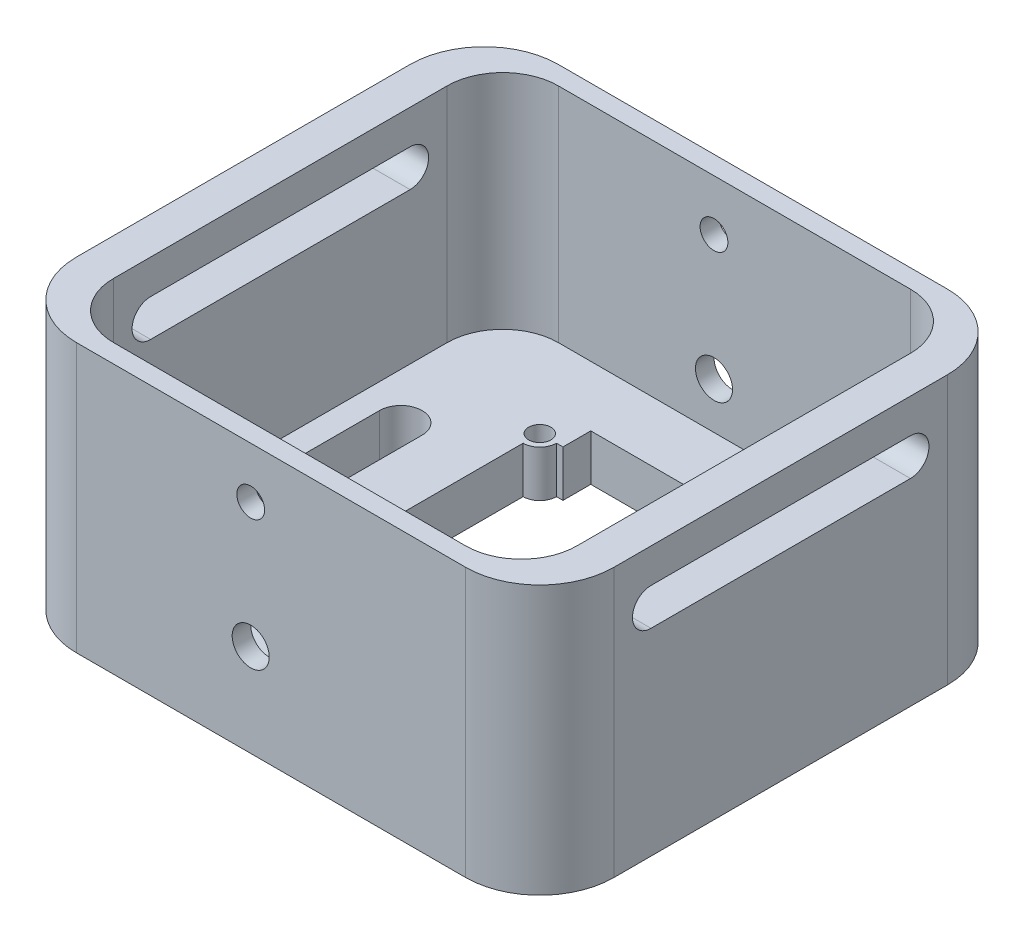
SolidWorks part; units mm, degrees
ref_plane "Front" through (0, 0, 0) normal (0, 0, 1) x (1, 0, 0)
ref_plane "Top" through (0, 0, 0) normal (0, 1, 0) x (1, 0, 0)
ref_plane "Right" through (0, 0, 0) normal (1, 0, 0) x (0, 0, -1)
sketch "Sketch1" plane through (0, 0, 0) normal (0, 1, 0) x (1, 0, 0)
  line L0 (1, 0) -> (12.5, 0) construction
  line L1 (-12.5, -12) -> (12.5, -12)
  line L2 (-12.5, -12) -> (-12.5, 12)
  line L3 (-12.5, 12) -> (12.5, 12)
  line L4 (12.5, -12) -> (12.5, 12)
  line L5 (-12.5, -12) -> (12.5, 12) construction
  line L6 (-12.5, 12) -> (12.5, -12) construction
  line L7 (1, 0) -> (1, 12) construction
  line L8 (10, -4) -> (10, 4) construction
  line L9 (8.85, -4) -> (8.85, 4)
  line L10 (11.15, -4) -> (11.15, 4)
  line L11 (0, 0) -> (0, 12) construction
  line L12 (-10, -4) -> (-10, 4) construction
  line L13 (-8.85, -4) -> (-8.85, 4)
  line L14 (-11.15, -4) -> (-11.15, 4)
  circle A0 centre (7.75, 7.25) radius 0.6
  circle A1 centre (7.75, -7.25) radius 0.6
  circle A2 centre (-5.75, -7.25) radius 0.6
  circle A3 centre (-5.75, 7.25) radius 0.6
  arc A4 (8.85, -4) -> (11.15, -4) centre (10, -4) ccw
  arc A5 (11.15, 4) -> (8.85, 4) centre (10, 4) ccw
  arc A6 (-8.85, -4) -> (-11.15, -4) centre (-10, -4) cw
  arc A7 (-11.15, 4) -> (-8.85, 4) centre (-10, 4) cw
  point P0 (0, 0)
  point P19 (10, 0)
  point P28 (-10, 0)
  dimension "D3" = 1.2
  dimension "D6" = 2.3
  dimension "D1" = 24
  dimension "D2" = 14.5
  dimension "D4" = 13.5
  dimension "D5" = 25
  dimension "D7" = 8
  dimension "D8" = 1
  dimension "D9" = 20
extrude "Boss-Extrude1" add sketch "Sketch1" along normal blind 2.5
sketch "Sketch3" plane through (0, 2.5, 0) normal (0, 1, 0) x (1, 0, 0)
  line L0 (-4.85, 7.25) -> (6.85, 7.25)
  line L1 (-5.75, 7.25) -> (7.75, 7.25) construction
  line L2 (-5.75, 7.25) -> (-5.75, -7.25) construction
  line L3 (-5.75, -7.25) -> (7.75, -7.25) construction
  line L4 (7.75, 7.25) -> (7.75, -7.25) construction
  line L5 (7.75, 6.35) -> (7.75, -6.35)
  line L6 (6.85, -7.25) -> (-4.85, -7.25)
  line L7 (-5.75, -6.35) -> (-5.75, 6.35)
  arc A0 (-4.85, 7.25) -> (-5.75, 6.35) centre (-5.75, 7.25) cw
  arc A1 (6.85, 7.25) -> (7.75, 6.35) centre (7.75, 7.25) ccw
  arc A2 (7.75, -6.35) -> (6.85, -7.25) centre (7.75, -7.25) ccw
  arc A3 (-5.75, -6.35) -> (-4.85, -7.25) centre (-5.75, -7.25) cw
  circle A4 centre (-5.75, 7.25) radius 0.6 construction
  dimension "D1" = 0.3
extrude "Cut-Extrude1" cut sketch "Sketch3" against normal through all
sketch "Sketch8" plane through (0, 2.5, 0) normal (0, 1, 0) x (1, 0, 0)
  line L0 (-5.75, 0) -> (7.75, 0) construction
  line L2 (7.75, -6.35) -> (7.75, 6.35) construction
  line L3 (-5.75, 6.35) -> (-5.75, -6.35) construction
  line L4 (-4.5, -8.75) -> (6.5, -8.75)
  line L5 (-4.5, -8.75) -> (-4.5, 8.75)
  line L6 (-4.5, 8.75) -> (6.5, 8.75)
  line L7 (6.5, -8.75) -> (6.5, 8.75)
  line L8 (-4.5, -8.75) -> (6.5, 8.75) construction
  line L9 (-4.5, 8.75) -> (6.5, -8.75) construction
  point P6 (1, 0)
  dimension "D1" = 11
  dimension "D2" = 17.5
extrude "Cut-Extrude4" cut sketch "Sketch8" against normal through all
sketch "Sketch2" plane through (0, 2.5, 0) normal (0, 1, 0) x (1, 0, 0)
  line L0 (14.5, -13) -> (14.5, 13)
  line L1 (14.5, 13) -> (-14.5, 13)
  line L2 (-14.5, 13) -> (-14.5, -13)
  line L3 (-14.5, -13) -> (14.5, -13)
  line L4 (12.5, -12) -> (12.5, 12)
  line L5 (12.5, 12) -> (-12.5, 12)
  line L6 (-12.5, 12) -> (-12.5, -12)
  line L7 (-12.5, -12) -> (12.5, -12)
  line L8 (12.5, -12) -> (12.5, 12)
  line L9 (12.5, 12) -> (-12.5, 12)
  line L10 (-12.5, 12) -> (-12.5, -12)
  line L11 (-12.5, -12) -> (12.5, -12)
  line L12 (14.5, 13) -> (-14.5, -13) construction
  dimension "D2" = 2
  dimension "D3" = 1
  dimension "D1" = 0
extrude "Boss-Extrude2" add sketch "Sketch2" against normal up to surface (2.5 mm away) and the other way blind 12 up to face at (1, 0, 0)
sketch "Sketch5" plane through (0, 0, -12) normal (0, 0, 1) x (1, 0, 0)
  line L0 (-1.1, 11) -> (-1.1, 2.5) construction
  line L1 (0, 0) -> (0, 14.5) construction
  line L4 (-12.5, 2.5) -> (12.5, 2.5)
  line L5 (12.5, 2.5) -> (12.5, 14.5)
  line L6 (12.5, 14.5) -> (-12.5, 14.5)
  line L7 (-12.5, 14.5) -> (-12.5, 2.5)
  line L8 (-12.5, 2.5) -> (12.5, 2.5) construction
  line L9 (12.5, 2.5) -> (12.5, 14.5) construction
  line L10 (12.5, 14.5) -> (-12.5, 14.5) construction
  line L11 (-12.5, 14.5) -> (-12.5, 2.5) construction
  circle A0 centre (-1.1, 11.75) radius 0.75
  circle A1 centre (-1.1, 5) radius 1
  dimension "D2" = 1.5
  dimension "D5" = 2
  dimension "D3" = 8.5
  dimension "D4" = 1.1
  dimension "D6" = 2.5
  dimension "D1" = 0
extrude "Cut-Extrude2" cut sketch "Sketch5" against normal through all both and the other way through all
fillet "Fillet1" radius 3 4 edges at (12.5, 8.5, 12) (-12.5, 8.5, 12) (-12.5, 8.5, -12) (12.5, 8.5, -12)
fillet "Fillet2" radius 4 4 edges at (-14.5, 7.25, -13) (14.5, 7.25, -13) (-14.5, 7.25, 13) (14.5, 7.25, 13)
sketch "Sketch9" plane through (14.5, 0, 0) normal (1, 0, 0) x (0, 0, -1)
  line L1 (-7, 11.65) -> (7, 11.65) construction
  line L2 (-7, 12.65) -> (7, 12.65)
  line L3 (-7, 10.65) -> (7, 10.65)
  line L5 (0, 11.65) -> (0, 14.5) construction
  line L6 (-9, 14.5) -> (9, 14.5) construction
  line L7 (-9, 2.5) -> (9, 2.5) construction
  arc A0 (-7, 12.65) -> (-7, 10.65) centre (-7, 11.65) ccw
  arc A1 (7, 10.65) -> (7, 12.65) centre (7, 11.65) ccw
  point P2 (0, 11.65)
  dimension "D1" = 9.15
  dimension "D2" = 14
  dimension "D3" = 2
extrude "Cut-Extrude5" cut sketch "Sketch9" against normal through all
